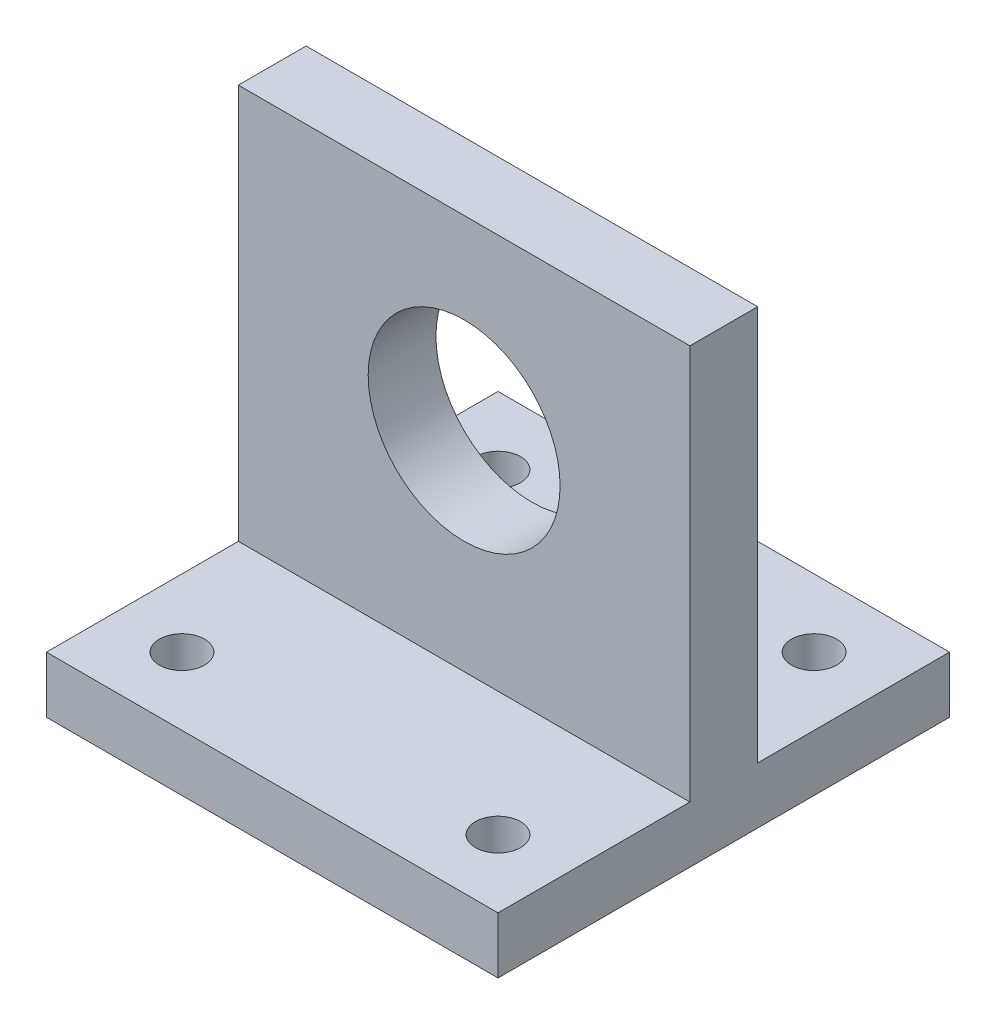
SolidWorks part; units mm, degrees
ref_plane "Front Plane" through (0, 0, 0) normal (0, 0, 1) x (1, 0, 0)
ref_plane "Top Plane" through (0, 0, 0) normal (0, 1, 0) x (1, 0, 0)
ref_plane "Right Plane" through (0, 0, 0) normal (1, 0, 0) x (0, 0, -1)
sketch "Sketch1" plane through (0, 0, 0) normal (0, 1, 0) x (1, 0, 0)
  line L1 (-20, -20) -> (20, -20)
  line L2 (-20, -20) -> (-20, 20)
  line L3 (-20, 20) -> (20, 20)
  line L4 (20, -20) -> (20, 20)
  line L5 (-20, -20) -> (20, 20) construction
  line L6 (-20, 20) -> (20, -20) construction
  point P0 (0, 0)
  dimension "D1" = 40
  dimension "D2" = 40
extrude "Boss-Extrude1" add sketch "Sketch1" along normal blind 5
sketch "Sketch2" plane through (0, 5, 0) normal (0, 1, 0) x (1, 0, 0)
  line L0 (20, -20) -> (20, 20) construction
  line L1 (-20, -3) -> (20, -3)
  line L2 (-20, -3) -> (-20, 3)
  line L3 (-20, 3) -> (20, 3)
  line L4 (20, -3) -> (20, 3)
  line L5 (-20, -3) -> (20, 3) construction
  line L6 (-20, 3) -> (20, -3) construction
  point P0 (0, 0)
  dimension "D1" = 6
extrude "Boss-Extrude2" add sketch "Sketch2" along normal blind 35
sketch "Sketch3" plane through (0, 5, 0) normal (0, 1, 0) x (1, 0, 0)
  line L0 (-20, 20) -> (-20, 3) construction
  line L1 (20, 3) -> (20, 20) construction
  line L2 (20, 20) -> (-20, 20) construction
  circle A0 centre (-14, 14) radius 2
  circle A1 centre (14, 14) radius 2
  point P6 (-20, 11.5)
  point P9 (20, 11.5)
  dimension "D5" = 4
  dimension "D6" = 4
  dimension "D1" = 6
  dimension "D2" = 6
  dimension "D3" = 6
  dimension "D4" = 6
extrude "Cut-Extrude1" cut sketch "Sketch3" against normal through all
mirror "Mirror1" about plane through (0, 0, 0) normal (0, 0, 1) of "Cut-Extrude1"
sketch "Sketch4" plane through (0, 0, 3) normal (0, 0, 1) x (1, 0, 0)
  line L0 (-20, 40) -> (20, 40) construction
  line L1 (-20, 0) -> (20, 0) construction
  circle A0 centre (0, 23.5) radius 8.5
  point P4 (0, 40)
  dimension "D1" = 17
  dimension "D2" = 23.5
extrude "Cut-Extrude2" cut sketch "Sketch4" against normal through all
